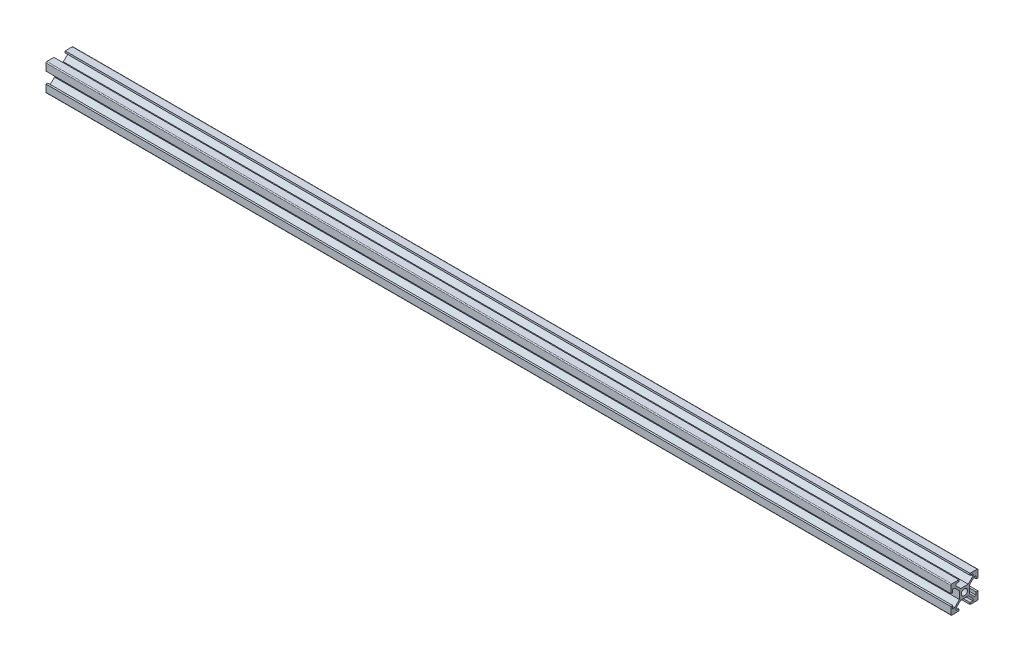
SolidWorks part; units mm, degrees
ref_plane "前视基准面" through (0, 0, 0) normal (0, 0, 1) x (1, 0, 0)
ref_plane "上视基准面" through (0, 0, 0) normal (0, 1, 0) x (1, 0, 0)
ref_plane "右视基准面" through (0, 0, 0) normal (1, 0, 0) x (0, 0, -1)
sketch "草图2" plane through (0, 0, 0) normal (1, 0, 0) x (0, 0, -1)
  line L0 (-3.1, 7.5) -> (3.1, 7.5)
  line L1 (-7, 7.5) -> (7, 7.5)
  line L2 (-7.5, 7) -> (-7.5, -7)
  line L3 (-7, -7.5) -> (7, -7.5)
  line L4 (7.5, 7) -> (7.5, -7)
  line L5 (-3.1, 7.5) -> (-3.1, 6.5)
  line L6 (-3.1, 6.5) -> (-4.7, 6.5)
  line L7 (-4.7, 6.5) -> (-4.7, 5.4071)
  line L8 (-4.7, 5.4071) -> (-2.0929, 2.8)
  line L9 (-2.0929, 2.8) -> (2.0929, 2.8)
  line L10 (2.0929, 2.8) -> (4.7, 5.4071)
  line L11 (4.7, 5.4071) -> (4.7, 6.5)
  line L12 (4.7, 6.5) -> (3.1, 6.5)
  line L13 (3.1, 6.5) -> (3.1, 7.5)
  line L14 (-7.5, -7.5) -> (7.5, 7.5) construction
  line L15 (7.5, -7.5) -> (-7.5, 7.5) construction
  line L17 (-2.8, 2.8) -> (2.8, 2.8)
  line L18 (-2.8, 2.8) -> (-2.8, -2.8)
  line L19 (-2.8, -2.8) -> (2.8, -2.8)
  line L20 (2.8, 2.8) -> (2.8, -2.8)
  line L21 (-2.8, 2.8) -> (2.8, -2.8) construction
  line L22 (-2.8, -2.8) -> (2.8, 2.8) construction
  line L52 (7.5, 3.1) -> (7.5, -3.1)
  line L53 (6.5, -3.1) -> (7.5, -3.1)
  line L54 (6.5, -4.7) -> (6.5, -3.1)
  line L55 (5.4071, -4.7) -> (6.5, -4.7)
  line L56 (2.8, -2.0929) -> (5.4071, -4.7)
  line L57 (2.8, 2.0929) -> (2.8, -2.0929)
  line L58 (5.4071, 4.7) -> (2.8, 2.0929)
  line L59 (6.5, 4.7) -> (5.4071, 4.7)
  line L60 (6.5, 3.1) -> (6.5, 4.7)
  line L61 (7.5, 3.1) -> (6.5, 3.1)
  line L62 (3.1, -7.5) -> (-3.1, -7.5)
  line L63 (-3.1, -6.5) -> (-3.1, -7.5)
  line L64 (-4.7, -6.5) -> (-3.1, -6.5)
  line L65 (-4.7, -5.4071) -> (-4.7, -6.5)
  line L66 (-2.0929, -2.8) -> (-4.7, -5.4071)
  line L67 (2.0929, -2.8) -> (-2.0929, -2.8)
  line L68 (4.7, -5.4071) -> (2.0929, -2.8)
  line L69 (4.7, -6.5) -> (4.7, -5.4071)
  line L70 (3.1, -6.5) -> (4.7, -6.5)
  line L71 (3.1, -7.5) -> (3.1, -6.5)
  line L72 (-7.5, -3.1) -> (-7.5, 3.1)
  line L73 (-6.5, 3.1) -> (-7.5, 3.1)
  line L74 (-6.5, 4.7) -> (-6.5, 3.1)
  line L75 (-5.4071, 4.7) -> (-6.5, 4.7)
  line L76 (-2.8, 2.0929) -> (-5.4071, 4.7)
  line L77 (-2.8, -2.0929) -> (-2.8, 2.0929)
  line L78 (-5.4071, -4.7) -> (-2.8, -2.0929)
  line L79 (-6.5, -4.7) -> (-5.4071, -4.7)
  line L80 (-6.5, -3.1) -> (-6.5, -4.7)
  line L81 (-7.5, -3.1) -> (-6.5, -3.1)
  line L82 (0, 0) -> (2.0929, 2.8) construction
  line L83 (0, 0) -> (2.8, -2.0929) construction
  circle A0 centre (0, 0) radius 1.65
  circle A1 centre (-7, 7) radius 0.5 construction
  circle A2 centre (-7, -7) radius 0.5 construction
  circle A3 centre (7, -7) radius 0.5 construction
  circle A4 centre (7, 7) radius 0.5 construction
  arc A5 (7, 7.5) -> (7.5, 7) centre (7, 7) cw
  arc A6 (7, -7.5) -> (7.5, -7) centre (7, -7) ccw
  arc A7 (-7.5, -7) -> (-7, -7.5) centre (-7, -7) ccw
  arc A8 (-7, 7.5) -> (-7.5, 7) centre (-7, 7) ccw
  point P16 (0, 0)
  point P50 (0, 7.5)
  point P52 (7.5, 0)
  dimension "D3" = 3.3
  dimension "D12" = 1
  dimension "D13" = 1
  dimension "D14" = 1
  dimension "D15" = 1
  dimension "D16" = 0.5
  dimension "D1" = 15
  dimension "D2" = 6.2
  dimension "D4" = 5.6
  dimension "D5" = 9.4
  dimension "D6" = 0.5
  dimension "D7" = 0.5
  dimension "D8" = 4.7
  dimension "D9" = 1
  dimension "D10" = 4
  dimension "D11" = 90
extrude "凸台-拉伸1" add sketch "草图2" along normal blind 500 contours L2 A7 L3 A6 L4 A5 L1 A8
extrude "切除-拉伸2" cut sketch "草图2<4>" against normal through all and the other way through all contours L3 L71 L70 L69 L68 L19 L66 L65 L64 L63 | L2 L81 L80 L79 L78 L18 L76 L75 L74 L73 | L12 L13 L0 L5 L6 L7 L8 L9 L10 L11 | L4 L61 L60 L59 L58 L20 L56 L55 L54 L53 | A0 region at (0, 5.2713, 0) region at (0, 0, 5.2713) region at (0, 0, -5.2713) region at (0, -5.2713, 0) region at (0, 0, 0)
sketch "草图2<4>" plane through (0, 0, 0) normal (1, 0, 0) x (0, 0, -1) same geometry as "草图2"
